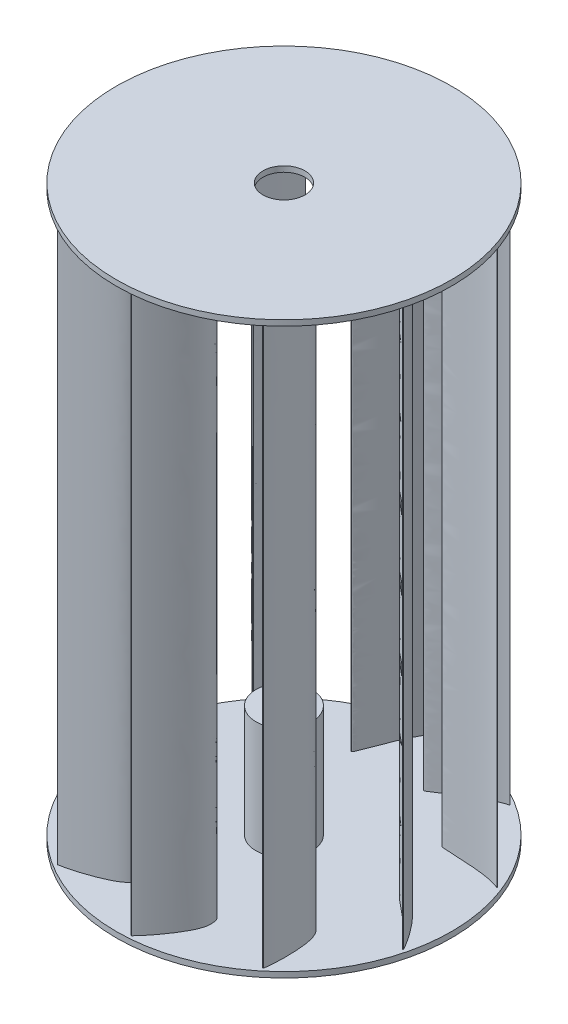
SolidWorks part; units mm, degrees
other "DetailItem5"
other "DetailItem6"
ref_plane "Front Plane" through (0, 0, 0) normal (0, 0, 1) x (1, 0, 0)
ref_plane "Top Plane" through (0, 0, 0) normal (0, 1, 0) x (1, 0, 0)
ref_plane "Right Plane" through (0, 0, 0) normal (1, 0, 0) x (0, 0, -1)
sketch "Sketch1" plane through (0, 0, 0) normal (0, 1, 0) x (1, 0, 0)
  circle A0 centre (0, 0) radius 60
  circle A1 centre (0, 0) radius 4.05
  dimension "D1" = 120
  dimension "D2" = 8.1
extrude "Boss-Extrude1" add sketch "Sketch1" along normal blind 2 contours A1 | A0 region at (0, 0, 0)
sketch "Sketch5" plane through (0, 2, 0) normal (0, 1, 0) x (1, 0, 0)
  line L0 (56.9833, -14.2559) -> (56.8247, -14.4742)
  line L1 (-76.6803, 0) -> (87.6071, 0) construction
  line L2 (54.4799, 21.9607) -> (54.4799, 21.6909)
  line L3 (37.721, -45.0272) -> (37.4645, -45.1106)
  line L4 (4.0506, -58.5997) -> (3.794, -58.5163)
  line L5 (-31.167, -49.789) -> (-31.3256, -49.5708)
  line L6 (-54.4799, -21.9607) -> (-54.4799, -21.6909)
  line L7 (-56.9833, 14.2559) -> (-56.8247, 14.4742)
  line L8 (-37.721, 45.0272) -> (-37.4645, 45.1106)
  line L9 (-4.0506, 58.5997) -> (-3.794, 58.5163)
  line L10 (31.167, 49.789) -> (31.3256, 49.5708)
  line L18 (-8.19, -1.6) -> (8.19, -1.6)
  line L19 (-8.19, -1.6) -> (-8.19, 1.6)
  line L20 (-8.19, 1.6) -> (8.19, 1.6)
  line L21 (8.19, -1.6) -> (8.19, 1.6)
  line L22 (-8.19, -1.6) -> (8.19, 1.6) construction
  line L23 (-8.19, 1.6) -> (8.19, -1.6) construction
  circle A0 centre (0, 0) radius 10
  circle A1 centre (0, 0) radius 40.3259 construction
  spline S0 degree 3 poles (31.7716, 24.8342) (31.7664, 24.792) (31.7598, 24.712) (31.9006, 24.5696) (32.0956, 24.5067) (32.4969, 24.4247) (37.402, 24.1921) (47.2098, 23.662) (51.9177, 22.649) (53.888, 21.9515) (54.4799, 21.6909) knots 0.499514 0.499514 0.499514 0.499514 0.508262 0.515116 0.518944 0.522858 0.530686 0.624525 0.81222 0.898706 0.898706 0.898706 0.898706
  spline S1 degree 3 poles (54.4799, 21.9607) (54.3716, 22.0176) (53.4297, 22.4997) (50.7376, 23.6588) (44.5297, 25.7581) (38.1375, 27.152) (34.4952, 26.8297) (32.0063, 25.4726) (31.8037, 25.096) (31.7716, 24.8342) knots 0.027203 0.027203 0.027203 0.027203 0.031297 0.062601 0.125217 0.250445 0.375468 0.445342 0.499514 0.499514 0.499514 0.499514
  spline S2 degree 3 poles (40.301, 1.4164) (40.2719, 1.3853) (40.2196, 1.3245) (40.2498, 1.1265) (40.3705, 0.961) (40.6471, 0.6588) (44.4786, -2.4125) (52.1017, -8.6063) (55.3151, -12.193) (56.4991, -13.9154) (56.8247, -14.4742) knots 0.499514 0.499514 0.499514 0.499514 0.508262 0.515116 0.518944 0.522858 0.530686 0.624525 0.81222 0.898706 0.898706 0.898706 0.898706
  spline S3 degree 3 poles (56.9833, -14.2559) (56.9292, -14.1462) (56.4505, -13.2026) (54.9538, -10.6825) (51.1655, -5.3352) (46.8134, -0.4502) (43.6773, 1.4299) (40.8661, 1.7949) (40.4808, 1.6094) (40.301, 1.4164) knots 0.027203 0.027203 0.027203 0.027203 0.031297 0.062601 0.125217 0.250445 0.375468 0.445342 0.499514 0.499514 0.499514 0.499514
  spline S4 degree 3 poles (33.4367, -22.5424) (33.3949, -22.5505) (33.3169, -22.5689) (33.2249, -22.7469) (33.2253, -22.9517) (33.2714, -23.3588) (34.5659, -28.0957) (37.0925, -37.5872) (37.5839, -42.3777) (37.5294, -44.4671) (37.4645, -45.1106) knots 0.499514 0.499514 0.499514 0.499514 0.508262 0.515116 0.518944 0.522858 0.530686 0.624525 0.81222 0.898706 0.898706 0.898706 0.898706
  spline S5 degree 3 poles (37.721, -45.0272) (37.7417, -44.9067) (37.9092, -43.8619) (38.1796, -40.9434) (38.2579, -34.3906) (37.6082, -27.8805) (36.1761, -24.5161) (34.1164, -22.5683) (33.6956, -22.492) (33.4367, -22.5424) knots 0.027203 0.027203 0.027203 0.027203 0.031297 0.062601 0.125217 0.250445 0.375468 0.445342 0.499514 0.499514 0.499514 0.499514
  spline S6 degree 3 poles (13.8008, -37.8908) (13.7622, -37.8728) (13.6882, -37.8418) (13.5092, -37.9317) (13.3891, -38.0977) (13.1872, -38.4541) (11.4502, -43.0472) (7.9152, -52.2111) (5.497, -56.3756) (4.2249, -58.0339) (3.794, -58.5163) knots 0.499514 0.499514 0.499514 0.499514 0.508262 0.515116 0.518944 0.522858 0.530686 0.624525 0.81222 0.898706 0.898706 0.898706 0.898706
  spline S7 degree 3 poles (4.0506, -58.5997) (4.1382, -58.5143) (4.8878, -57.7675) (6.822, -55.5653) (10.737, -50.31) (14.038, -44.6614) (14.8569, -41.0977) (14.3354, -38.3113) (14.0398, -38.0022) (13.8008, -37.8908) knots 0.027203 0.027203 0.027203 0.027203 0.031297 0.062601 0.125217 0.250445 0.375468 0.445342 0.499514 0.499514 0.499514 0.499514
  spline S8 degree 3 poles (-11.1066, -38.7662) (-11.1272, -38.729) (-11.1689, -38.6604) (-11.3665, -38.6279) (-11.5612, -38.6916) (-11.9341, -38.8612) (-16.0391, -41.5562) (-24.2854, -46.8922) (-28.6895, -48.8399) (-30.6935, -49.4337) (-31.3256, -49.5708) knots 0.499514 0.499514 0.499514 0.499514 0.508262 0.515116 0.518944 0.522858 0.530686 0.624525 0.81222 0.898706 0.898706 0.898706 0.898706
  spline S9 degree 3 poles (-31.167, -49.789) (-31.0459, -49.7715) (-30.0006, -49.6078) (-27.1413, -48.9631) (-20.8851, -47.0127) (-14.8943, -44.3831) (-12.1371, -41.9814) (-10.9212, -39.4206) (-10.9787, -38.9969) (-11.1066, -38.7662) knots 0.027203 0.027203 0.027203 0.027203 0.031297 0.062601 0.125217 0.250445 0.375468 0.445342 0.499514 0.499514 0.499514 0.499514
  spline S10 degree 3 poles (-31.7716, -24.8342) (-31.7664, -24.792) (-31.7598, -24.712) (-31.9006, -24.5696) (-32.0956, -24.5067) (-32.4969, -24.4247) (-37.402, -24.1921) (-47.2098, -23.662) (-51.9177, -22.649) (-53.888, -21.9515) (-54.4799, -21.6909) knots 0.499514 0.499514 0.499514 0.499514 0.508262 0.515116 0.518944 0.522858 0.530686 0.624525 0.81222 0.898706 0.898706 0.898706 0.898706
  spline S11 degree 3 poles (-54.4799, -21.9607) (-54.3716, -22.0176) (-53.4297, -22.4997) (-50.7376, -23.6588) (-44.5297, -25.7581) (-38.1375, -27.152) (-34.4952, -26.8297) (-32.0063, -25.4726) (-31.8037, -25.096) (-31.7716, -24.8342) knots 0.027203 0.027203 0.027203 0.027203 0.031297 0.062601 0.125217 0.250445 0.375468 0.445342 0.499514 0.499514 0.499514 0.499514
  spline S12 degree 3 poles (-40.301, -1.4164) (-40.2719, -1.3853) (-40.2196, -1.3245) (-40.2498, -1.1265) (-40.3705, -0.961) (-40.6471, -0.6588) (-44.4786, 2.4125) (-52.1017, 8.6063) (-55.3151, 12.193) (-56.4991, 13.9154) (-56.8247, 14.4742) knots 0.499514 0.499514 0.499514 0.499514 0.508262 0.515116 0.518944 0.522858 0.530686 0.624525 0.81222 0.898706 0.898706 0.898706 0.898706
  spline S13 degree 3 poles (-56.9833, 14.2559) (-56.9292, 14.1462) (-56.4505, 13.2026) (-54.9538, 10.6825) (-51.1655, 5.3352) (-46.8134, 0.4502) (-43.6773, -1.4299) (-40.8661, -1.7949) (-40.4808, -1.6094) (-40.301, -1.4164) knots 0.027203 0.027203 0.027203 0.027203 0.031297 0.062601 0.125217 0.250445 0.375468 0.445342 0.499514 0.499514 0.499514 0.499514
  spline S14 degree 3 poles (-33.4367, 22.5424) (-33.3949, 22.5505) (-33.3169, 22.5689) (-33.2249, 22.7469) (-33.2253, 22.9517) (-33.2714, 23.3588) (-34.5659, 28.0957) (-37.0925, 37.5872) (-37.5839, 42.3777) (-37.5294, 44.4671) (-37.4645, 45.1106) knots 0.499514 0.499514 0.499514 0.499514 0.508262 0.515116 0.518944 0.522858 0.530686 0.624525 0.81222 0.898706 0.898706 0.898706 0.898706
  spline S15 degree 3 poles (-37.721, 45.0272) (-37.7417, 44.9067) (-37.9092, 43.8619) (-38.1796, 40.9434) (-38.2579, 34.3906) (-37.6082, 27.8805) (-36.1761, 24.5161) (-34.1164, 22.5683) (-33.6956, 22.492) (-33.4367, 22.5424) knots 0.027203 0.027203 0.027203 0.027203 0.031297 0.062601 0.125217 0.250445 0.375468 0.445342 0.499514 0.499514 0.499514 0.499514
  spline S16 degree 3 poles (-13.8008, 37.8908) (-13.7622, 37.8728) (-13.6882, 37.8418) (-13.5092, 37.9317) (-13.3891, 38.0977) (-13.1872, 38.4541) (-11.4502, 43.0472) (-7.9152, 52.2111) (-5.497, 56.3756) (-4.2249, 58.0339) (-3.794, 58.5163) knots 0.499514 0.499514 0.499514 0.499514 0.508262 0.515116 0.518944 0.522858 0.530686 0.624525 0.81222 0.898706 0.898706 0.898706 0.898706
  spline S17 degree 3 poles (-4.0506, 58.5997) (-4.1382, 58.5143) (-4.8878, 57.7675) (-6.822, 55.5653) (-10.737, 50.31) (-14.038, 44.6614) (-14.8569, 41.0977) (-14.3354, 38.3113) (-14.0398, 38.0022) (-13.8008, 37.8908) knots 0.027203 0.027203 0.027203 0.027203 0.031297 0.062601 0.125217 0.250445 0.375468 0.445342 0.499514 0.499514 0.499514 0.499514
  spline S18 degree 3 poles (11.1066, 38.7662) (11.1272, 38.729) (11.1689, 38.6604) (11.3665, 38.6279) (11.5612, 38.6916) (11.9341, 38.8612) (16.0391, 41.5562) (24.2854, 46.8922) (28.6895, 48.8399) (30.6935, 49.4337) (31.3256, 49.5708) knots 0.499514 0.499514 0.499514 0.499514 0.508262 0.515116 0.518944 0.522858 0.530686 0.624525 0.81222 0.898706 0.898706 0.898706 0.898706
  spline S19 degree 3 poles (31.167, 49.789) (31.0459, 49.7715) (30.0006, 49.6078) (27.1413, 48.9631) (20.8851, 47.0127) (14.8943, 44.3831) (12.1371, 41.9814) (10.9212, 39.4206) (10.9787, 38.9969) (11.1066, 38.7662) knots 0.027203 0.027203 0.027203 0.027203 0.031297 0.062601 0.125217 0.250445 0.375468 0.445342 0.499514 0.499514 0.499514 0.499514
  point P41 (0, 0)
  point P57 (0, 0)
  circle M2 centre (0, 0) radius 4.05
  dimension "D3" = 80.6517
  dimension "D2" = 20
  dimension "D1" = 10
  dimension "D4" = 16.38
  dimension "D5" = 3.2
extrude "Boss-Extrude3" add sketch "Sketch5" along normal blind 200 contours L2 S1 S0 | L10 S19 S18 | L9 S17 S16 | L6 S11 S10 | L5 S9 S8 | L3 S5 S4 | L0 S3 S2 | S15 S14 L8 | S13 S12 L7 | S6 L4 S7 region at (47.764, 2, 3.8908) region at (40.9286, 2, -24.9272) region at (36.3549, 2, 31.2227) region at (-18.4566, 2, 44.23) region at (-40.9281, 2, 24.9273) region at (-11.0599, 2, -46.6273) region at (18.4598, 2, -44.2235)
ref_plane "Plane1" through (0, 202, 0) normal (0, 1, 0) x (1, 0, 0)
sketch "Sketch6" plane through (0, 202, 0) normal (0, 1, 0) x (1, 0, 0)
  circle A0 centre (0, 0) radius 60
  dimension "D1" = 120
extrude "Boss-Extrude4" add sketch "Sketch6" along normal blind 2
extrude "Cut-Extrude1" cut sketch "Sketch5<3>" against normal up to surface (2 mm away) contours L18 L21 L20 L19 up to face at (0, 0, 60)
sketch "Sketch5<3>" plane through (0, 2, 0) normal (0, 1, 0) x (1, 0, 0) same geometry as "Sketch5"
sketch "Sketch7" plane through (0, 204, 0) normal (0, 1, 0) x (1, 0, 0)
  circle A0 centre (0, 0) radius 7.5
  dimension "D1" = 15
extrude "Boss-Extrude5" add sketch "Sketch5<5>" along normal blind 19.5 contours A0 L21 L18 L19 L20 M2 region at (-9.7172, 2, 0)
sketch "Sketch5<5>" plane through (0, 2, 0) normal (0, 1, 0) x (1, 0, 0) same geometry as "Sketch5"
sketch "Sketch8" plane through (0, 21.5, 0) normal (0, 1, 0) x (1, 0, 0)
  circle A0 centre (0, 0) radius 10 construction
  circle A1 centre (0, 0) radius 10
  circle A2 centre (0, 0) radius 4.05
extrude "Boss-Extrude6" add sketch "Sketch8" along normal blind 20.5
extrude "Cut-Extrude2" cut sketch "Sketch7" against normal up to surface (2 mm away) up to face at (46.9105, 202, -22.8736)
